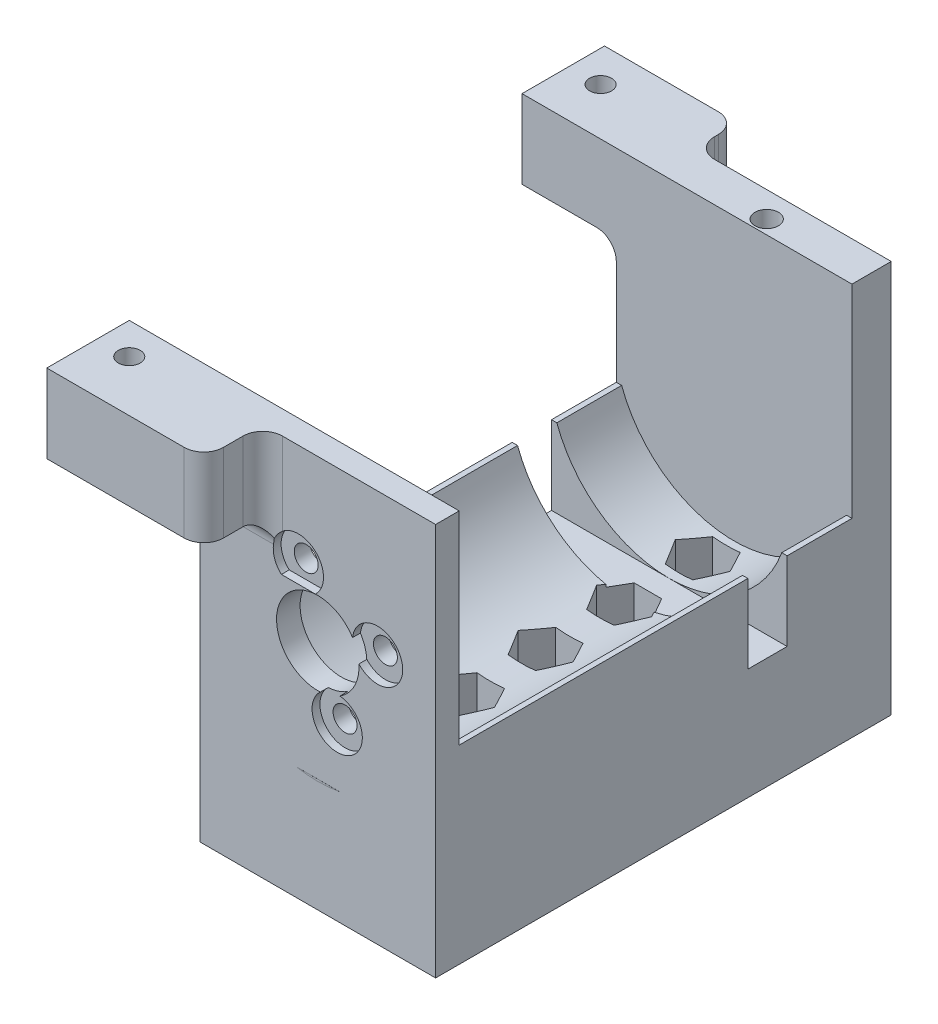
SolidWorks part; units mm, degrees
ref_plane "Front Plane" through (0, 0, 0) normal (0, 0, 1) x (1, 0, 0)
ref_plane "Top Plane" through (0, 0, 0) normal (0, 1, 0) x (1, 0, 0)
ref_plane "Right Plane" through (0, 0, 0) normal (1, 0, 0) x (0, 0, -1)
sketch "Sketch1" plane through (0, 0, 0) normal (0, 0, 1) x (1, 0, 0)
  line L1 (-15, -15) -> (15, -15)
  line L5 (-15, -15) -> (-15, -5.25)
  line L6 (15, -15) -> (15, 13)
  line L9 (-15, 13) -> (15, 13)
  line L11 (0, -5.25) -> (-15, -5.25)
  line L12 (0, 5.25) -> (-15, 5.25)
  line L13 (-15, 5.25) -> (-15, 13)
  line L14 (0, 0) -> (0, 8) construction
  line L15 (2.4721, -7.6085) -> (-2.4721, 7.6085) construction
  line L16 (0, 0) -> (7.6085, 2.4721) construction
  arc A0 (0, -5.25) -> (5.25, 0) centre (0, 0) ccw
  circle A1 centre (0, 0) radius 8 construction
  arc A5 (0, 5.25) -> (5.25, 0) centre (0, 0) cw
  circle A7 centre (-2.4721, 7.6085) radius 1.525
  circle A10 centre (7.6085, 2.4721) radius 1.525
  circle A11 centre (2.4721, -7.6085) radius 1.525
  dimension "D2" = 10.5
  dimension "D5" = 16
  dimension "D6" = 18
  dimension "D8" = 3.05
  dimension "D1" = 30
  dimension "D3" = 28
  dimension "D7" = 90
extrude "Boss-Extrude1" add sketch "Sketch1" along normal blind 3
sketch "Sketch2" plane through (0, 0, 3) normal (0, 0, 1) x (1, 0, 0)
  line L0 (-15, -15) -> (-15, -5.25)
  line L2 (-15, -15) -> (-15, -29.425)
  line L3 (-15, -29.425) -> (15, -29.425)
  line L4 (15, -15) -> (15, -29.425)
  line L6 (15, -15) -> (15, -5.25)
  line L8 (-15, -5.25) -> (-14.3178, -5.25)
  line L9 (0, -5.25) -> (-15, -5.25) construction
  line L10 (-14.3178, -5.25) -> (16.0436, -5.25) construction
  line L11 (15, -5.25) -> (14.3178, -5.25)
  arc A0 (-14.3178, -5.25) -> (14.3178, -5.25) centre (0, 0) ccw
  dimension "D2" = 30.5
  dimension "D4" = 15.25
  dimension "D1" = 14.425
  dimension "D3" = 14.425
extrude "Boss-Extrude2" add sketch "Sketch2" against normal blind 53
sketch "Sketch3" plane through (0, -29.425, 0) normal (0, -1, 0) x (-1, 0, 0)
  line L0 (0, -3) -> (0, 50) construction
  line L1 (15, -3) -> (-15, -3) construction
  line L2 (15, 50) -> (-15, 50) construction
  circle A0 centre (0, 46) radius 1.55
  circle A1 centre (0, 36) radius 1.55
  circle A2 centre (0, 26) radius 1.55
  circle A3 centre (0, 16) radius 1.55
  circle A4 centre (0, 6) radius 1.55
  dimension "D1" = 3.1
  dimension "D2" = 4
  dimension "D3" = 5
extrude "Cut-Extrude1" cut sketch "Sketch3" against normal through all
sketch "Sketch4" plane through (0, 0, 3) normal (0, 0, 1) x (1, 0, 0)
  line L0 (-2.75, -15) -> (2.694, -15.0102)
  arc A0 (-2.75, -15) -> (2.694, -15.0102) centre (0, 0) ccw
extrude "Boss-Extrude3" add sketch "Sketch4" against normal blind 3 separate body
sketch "Sketch7" plane through (0, 0, -50) normal (0, 0, -1) x (-1, 0, 0)
  line L0 (15, 13) -> (15, 2.75) construction
  line L1 (-15, -29.425) -> (15, -29.425)
  line L2 (-15, -29.425) -> (-15, 20.575)
  line L3 (-15, 20.575) -> (15, 20.575)
  line L4 (15, -29.425) -> (15, 20.575)
  dimension "D1" = 50
extrude "Boss-Extrude4" add sketch "Sketch7" along normal blind 5
sketch "Sketch9" plane through (-15, 0, 0) normal (-1, 0, 0) x (0, 0, 1)
  line L5 (3, -5.25) -> (-50, -5.25) construction
  line L6 (-41.75, -15.25) -> (-36.75, -15.25)
  line L9 (-41.75, -15.25) -> (-41.75, 4.75)
  line L10 (-41.75, 4.75) -> (-36.75, 4.75)
  line L11 (-36.75, -15.25) -> (-36.75, 4.75)
  line L12 (-41.75, -15.25) -> (-36.75, 4.75) construction
  line L13 (-41.75, 4.75) -> (-36.75, -15.25) construction
  line L14 (3, -5.25) -> (3, -29.425) construction
  point P0 (-39.25, -5.25)
  dimension "D1" = 42.25
  dimension "D2" = 5
  dimension "D3" = 20
extrude "Cut-Extrude6" cut sketch "Sketch9" against normal through all
sketch "Sketch11" plane through (0, 20.575, 0) normal (0, 1, 0) x (1, 0, 0)
  line L0 (-15, 50) -> (-27, 50)
  line L1 (-27, 50) -> (-27, 60.5)
  line L2 (-27, 60.5) -> (-10, 60.5)
  line L4 (-15, 55) -> (15, 55) construction
  line L6 (-15, 55) -> (-15, 50)
  line L10 (-10, 60.5) -> (-10, 55)
  line L11 (-10, 55) -> (-15, 55)
  circle A0 centre (-23, 56) radius 1.4
  dimension "D4" = 2.8
  dimension "D5" = 4.5
  dimension "D1" = 5.5
  dimension "D2" = 12
  dimension "D3" = 17
  dimension "D6" = 4
extrude "Boss-Extrude5" add sketch "Sketch11" against normal blind 10 contours L2 L10 L11 L6 L0 L1 | A0
sketch "Sketch12" plane through (0, 20.575, 0) normal (0, 1, 0) x (1, 0, 0)
  line L0 (-15, 41.75) -> (-15, 50) construction
  line L2 (-10, 55) -> (15, 55) construction
  circle A0 centre (2.4, 51.75) radius 1.5
  dimension "D3" = 3
  dimension "D1" = 17.4
  dimension "D2" = 3.25
extrude "Cut-Extrude8" cut sketch "Sketch12" against normal blind 10
sketch "Sketch5" plane through (0, -29.425, 0) normal (0, -1, 0) x (-1, 0, 0)
  line L0 (3.493, 36) -> (1.7465, 39.025)
  line L1 (3.493, 46) -> (1.7465, 49.025)
  line L2 (1.7465, 49.025) -> (-1.7465, 49.025)
  line L3 (-1.7465, 49.025) -> (-3.493, 46)
  line L4 (-3.493, 46) -> (-1.7465, 42.975)
  line L5 (-1.7465, 42.975) -> (1.7465, 42.975)
  line L6 (1.7465, 42.975) -> (3.493, 46)
  line L7 (1.7465, 39.025) -> (-1.7465, 39.025)
  line L8 (-1.7465, 39.025) -> (-3.493, 36)
  line L9 (-3.493, 36) -> (-1.7465, 32.975)
  line L10 (-1.7465, 32.975) -> (1.7465, 32.975)
  line L11 (1.7465, 32.975) -> (3.493, 36)
  line L12 (3.493, 26) -> (1.7465, 29.025)
  line L13 (1.7465, 29.025) -> (-1.7465, 29.025)
  line L14 (-1.7465, 29.025) -> (-3.493, 26)
  line L15 (-3.493, 26) -> (-1.7465, 22.975)
  line L16 (-1.7465, 22.975) -> (1.7465, 22.975)
  line L17 (1.7465, 22.975) -> (3.493, 26)
  line L18 (3.493, 16) -> (1.7465, 19.025)
  line L19 (1.7465, 19.025) -> (-1.7465, 19.025)
  line L20 (-1.7465, 19.025) -> (-3.493, 16)
  line L21 (-3.493, 16) -> (-1.7465, 12.975)
  line L22 (-1.7465, 12.975) -> (1.7465, 12.975)
  line L23 (1.7465, 12.975) -> (3.493, 16)
  line L24 (3.493, 6) -> (1.7465, 9.025)
  line L25 (1.7465, 9.025) -> (-1.7465, 9.025)
  line L26 (-1.7465, 9.025) -> (-3.493, 6)
  line L27 (-3.493, 6) -> (-1.7465, 2.975)
  line L28 (-1.7465, 2.975) -> (1.7465, 2.975)
  line L29 (1.7465, 2.975) -> (3.493, 6)
  circle A5 centre (0, 46) radius 3.025 construction
  circle A6 centre (0, 36) radius 3.025 construction
  circle A7 centre (0, 26) radius 3.025 construction
  circle A8 centre (0, 16) radius 3.025 construction
  circle A9 centre (0, 6) radius 3.025 construction
  dimension "D1" = 6.05
  dimension "D2" = 5
extrude "Cut-Extrude2" cut sketch "Sketch5" against normal through all from offset 5 contours L24 L25 L26 L27 L28 L29 | L18 L19 L20 L21 L22 L23 | L12 L13 L14 L15 L16 L17 | L0 L7 L8 L9 L10 L11 | L1 L2 L3 L4 L5 L6 offset against normal yes
sketch "Sketch6" plane through (0, 0, 3) normal (0, 0, 1) x (1, 0, 0)
  circle A1 centre (2.4721, -7.6085) radius 3.2
  circle A4 centre (-2.4721, 7.6085) radius 3.2
  circle A5 centre (7.6085, 2.4721) radius 3.2
  dimension "D1" = 6.4
extrude "Cut-Extrude3" cut sketch "Sketch6" against normal blind 1
sketch "Sketch17" plane through (0, 20.575, 0) normal (0, 1, 0) x (1, 0, 0)
  line L0 (-15, 0) -> (-27, 0)
  line L1 (-27, 0) -> (-27, -10.5)
  line L2 (-27, -10.5) -> (-7.0075, -10.5)
  line L3 (-7.0075, -10.5) -> (-7.0075, -3)
  line L6 (-7.0075, -3) -> (-7.0075, 0)
  line L7 (-2.75, 0) -> (-14.3178, 0) construction
  line L8 (-7.0075, 0) -> (-15, 0)
  circle A0 centre (-23, -4) radius 1.4
  dimension "D4" = 2.8
  dimension "D5" = 4
  dimension "D6" = 4
  dimension "D1" = 12
  dimension "D2" = 10.5
  dimension "D3" = 7.5
extrude "Boss-Extrude8" add sketch "Sketch17" against normal up to surface (10 mm away) up to face at (-23, 10.575, -54.6)
sketch "Sketch19" plane through (0, 0, 3) normal (0, 0, 1) x (1, 0, 0)
  line L4 (-15, -5.25) -> (0, -5.25)
  line L5 (0, 5.25) -> (-15, 5.25)
  line L6 (-15, -5.25) -> (-15, 10.575) construction
  line L7 (-15, 5.25) -> (-15, -5.25)
  arc A0 (0, 5.25) -> (0, -5.25) centre (0, 0) ccw
extrude "Boss-Extrude10" add sketch "Sketch19" against normal up to surface (3 mm away) up to face at (-4.4832, 3.1949, 0)
sketch "Sketch20" plane through (0, 13, 0) normal (0, 1, 0) x (1, 0, 0)
  line L1 (-7.0075, 0) -> (15, 0)
  line L2 (-7.0075, 0) -> (-7.0075, -3)
  line L3 (-7.0075, -3) -> (15, -3)
  line L4 (15, 0) -> (15, -3)
extrude "Boss-Extrude11" add sketch "Sketch20" along normal up to surface (7.575 mm away) up to face at (-23, 20.575, 5.4)
fillet "Fillet3" radius 2.5 7 edges at (-10, 15.575, -60.5) (-10, 15.575, -55) (-12.5, 10.575, -55) (-15, 10.575, 1.5) (-11.0037, 10.575, 3) (-7.0075, 15.575, 10.5) (-7.0075, 15.575, 3)
fillet "Fillet2" radius 2.5 1 edges at (-15, 10.575, -53.75)
